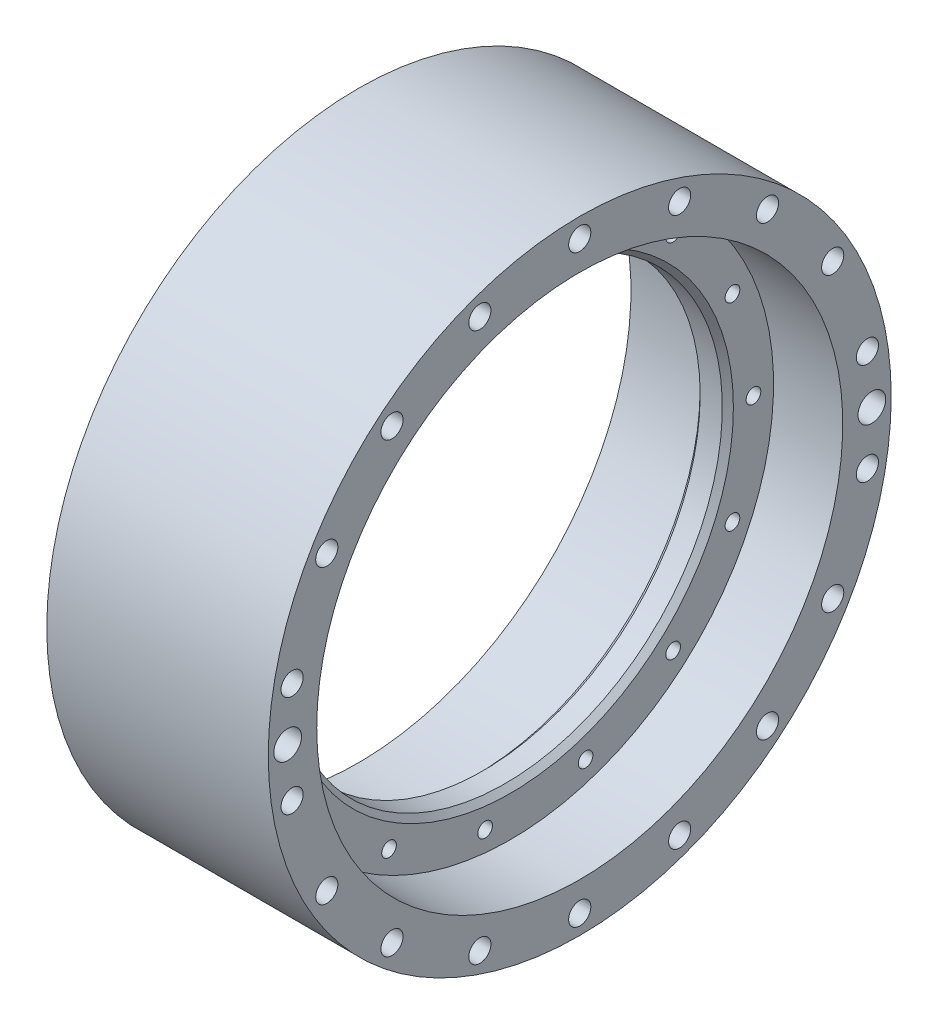
SolidWorks part; units mm, degrees
ref_plane "Front Plane" through (0, 0, 0) normal (0, 0, 1) x (1, 0, 0)
ref_plane "Top Plane" through (0, 0, 0) normal (0, 1, 0) x (1, 0, 0)
ref_plane "Right Plane" through (0, 0, 0) normal (1, 0, 0) x (0, 0, -1)
sketch "Sketch1" plane through (0, 0, 0) normal (0, 0, 1) x (1, 0, 0)
  line L0 (0, 112.5) -> (80, 112.5)
  line L1 (80, 112.5) -> (80, 95)
  line L3 (55, 95) -> (55, 78.5)
  line L4 (55, 78.5) -> (43, 78.5)
  line L5 (43, 78.5) -> (43, 98.5)
  line L6 (43, 98.5) -> (0, 98.5)
  line L7 (0, 98.5) -> (0, 112.5)
  line L8 (0, 0) -> (89.4597, 0) construction
  line L9 (27.6099, 87.75) -> (95.1089, 87.75) construction
  line L10 (55, 95) -> (80, 95)
  dimension "D1" = 98.5
  dimension "D2" = 112.5
  dimension "D3" = 25
  dimension "D4" = 12
  dimension "D5" = 20
  dimension "D6" = 80
  dimension "D7" = 87.75
  dimension "D8" = 95
revolve "Revolve1" add sketch "Sketch1" angle 360 about L8
sketch "Sketch2" plane through (0, 0, 0) normal (-1, 0, 0) x (0, 0, 1)
  line L0 (0, 112.5) -> (0, 98.5) construction
  circle A1 centre (0, 0) radius 112.5 construction
  circle A2 centre (0, 0) radius 98.5 construction
  point P0 (0, 105.5)
hole_wizard "Ø8.0mm Dowel Hole1" positions "3DSketch1" profile "Sketch3" hole size "Ø8.0" standard "ISO" end condition through all
sketch3d "3DSketch1"
  point P0 (0, 105.5, 0)
sketch "Sketch3" plane through (0, 105.5, 0) normal (0, 1, 0) x (0, 0, 1)
  line L0 (0, 0) -> (0, 80)
  line L1 (0, 80) -> (4, 80)
  line L2 (4, 80) -> (4, 0)
  line L5 (4, 0) -> (0, 0)
  line L11 (0, -6.35) -> (0, 107.95) construction
  dimension "Thru Hole Dia." = 8
  dimension "Thru Hole Depth" = 80
ref_axis "Axis1" through (80, 0, 0) along (-1, 0, 0)
pattern_circular "CirPattern1" count 18 over 360 about axis through (80, 0, 0) along (-1, 0, 0) of "Ø8.0mm Dowel Hole1"
sketch "Sketch4" plane through (0, 0, 0) normal (-1, 0, 0) x (0, 0, 1)
  line L0 (112.5, 0) -> (98.5, 0) construction
  line L1 (0, 0) -> (0, 33.1049) construction
  circle A0 centre (0, 0) radius 112.5 construction
  circle A1 centre (0, 0) radius 98.5 construction
  circle A2 centre (105.5, 0) radius 5
  circle A3 centre (-105.5, 0) radius 5
  dimension "D1" = 10
extrude "Cut-Extrude1" cut sketch "Sketch4" against normal through all
sketch "Sketch5" plane through (55, 0, 0) normal (1, 0, 0) x (0, 0, -1)
  circle A0 centre (87.75, 0) radius 2.65
  circle A3 centre (0, 0) radius 87.75 construction
  point P4 (0, 0)
  point P5 (0, 81.1234)
  point P6 (0, 0)
  point P7 (0, 0)
  dimension "D1" = 5.3
  dimension "D2" = 175.5
extrude "Cut-Extrude2" cut sketch "Sketch5" against normal through all
pattern_circular "CirPattern2" count 15 over 360 about axis through (80, 0, 0) along (-1, 0, 0) of "Cut-Extrude2"
chamfer "Chamfer1" distance 2 angle 45 2 edges at (43, 0, 78.5) (55, 0, 78.5)
